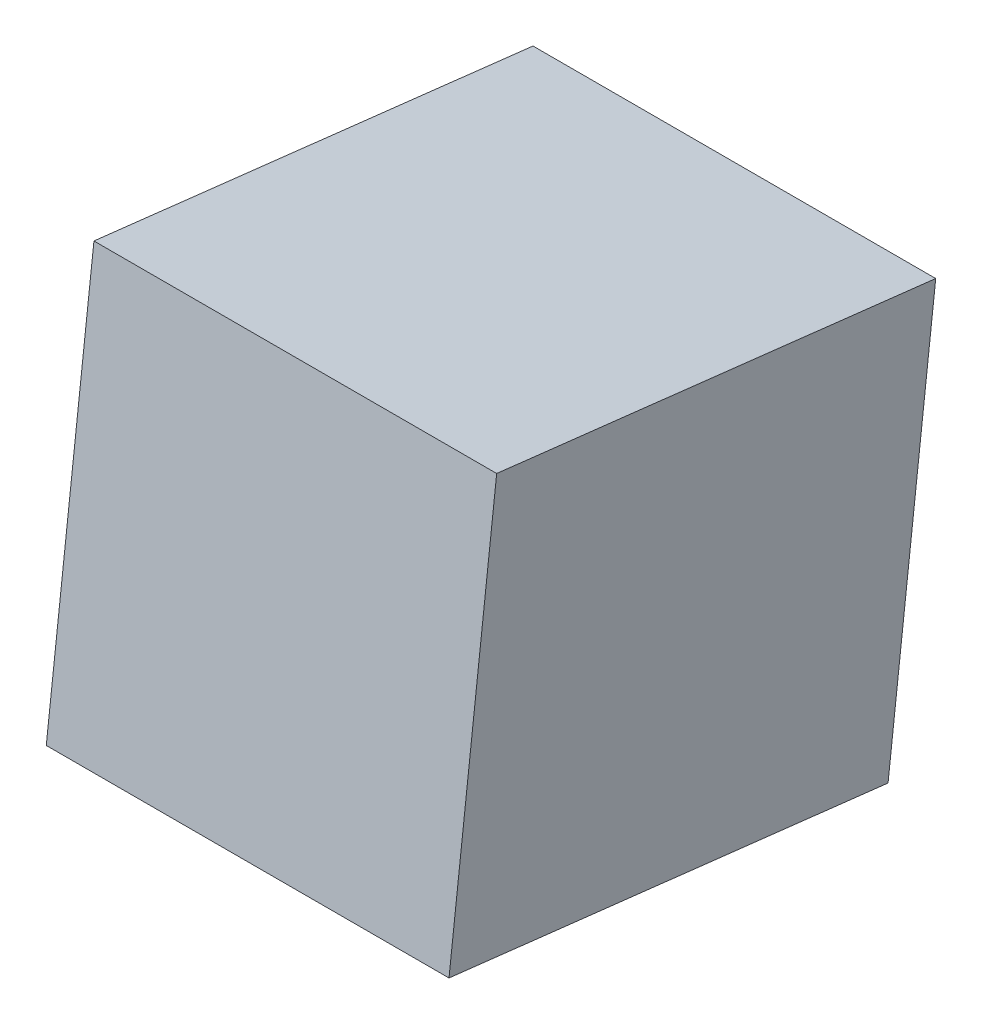
SolidWorks part; units mm, degrees
ref_plane "Front Plane" through (0, 0, 0) normal (0, 0, 1) x (1, 0, 0)
ref_plane "Top Plane" through (0, 0, 0) normal (0, 1, 0) x (1, 0, 0)
ref_plane "Right Plane" through (0, 0, 0) normal (1, 0, 0) x (0, 0, -1)
sketch "Sketch1" plane through (0, 358.8799, -41.4225) normal (0, 0.9934, -0.1147) x (1, 0, 0)
  line L1 (-212, 126.857) -> (-58, 126.857)
  line L2 (-212, 126.857) -> (-212, 295.857)
  line L3 (-212, 295.857) -> (-58, 295.857)
  line L4 (-58, 126.857) -> (-58, 295.857)
  line L5 (-212, 126.857) -> (-58, 295.857) construction
  line L6 (-212, 295.857) -> (-58, 126.857) construction
  point P0 (-135, 211.357)
  dimension "D1" = 169
  dimension "D2" = 154
extrude "Boss-Extrude1" add sketch "Sketch1" along normal blind 159
